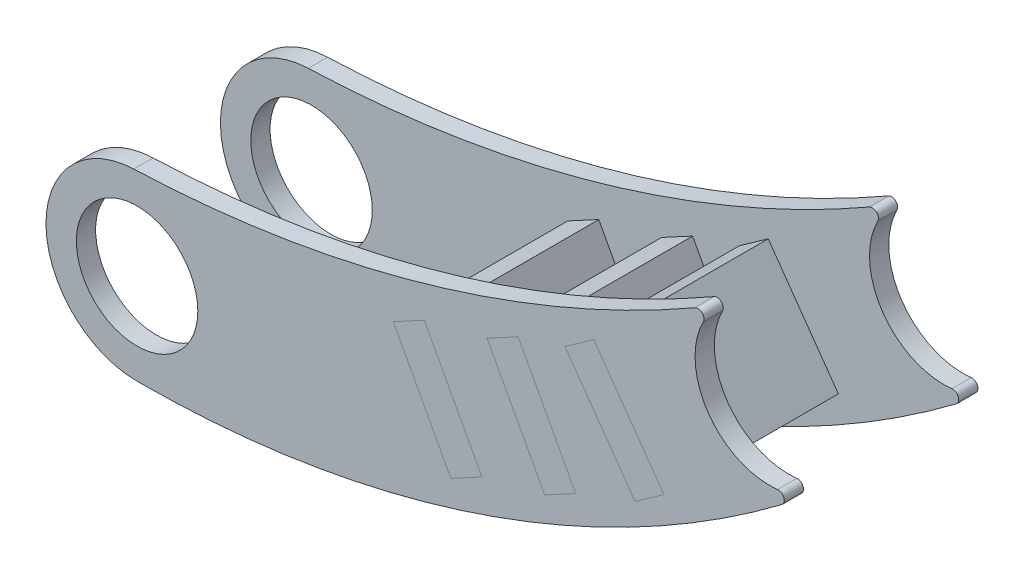
SolidWorks part; units mm, degrees
ref_plane "Front Plane" through (0, 0, 0) normal (0, 0, 1) x (1, 0, 0)
ref_plane "Top Plane" through (0, 0, 0) normal (0, 1, 0) x (1, 0, 0)
ref_plane "Right Plane" through (0, 0, 0) normal (1, 0, 0) x (0, 0, -1)
sketch "Sketch1" plane through (0, 0, 0) normal (0, 0, 1) x (1, 0, 0)
  line L17 (0, 0) -> (120, 0) construction
  line L18 (51.668, -3.0181) -> (42.1892, 14.5931)
  line L19 (51.668, -3.0181) -> (56.7793, -0.2671)
  line L20 (42.1892, 14.5931) -> (47.3005, 17.3441)
  line L21 (56.7793, -0.2671) -> (47.3005, 17.3441)
  line L22 (51.668, -3.0181) -> (47.3005, 17.3441) construction
  line L23 (42.1892, 14.5931) -> (56.7793, -0.2671) construction
  line L24 (67.1116, 2.3473) -> (57.6329, 19.9584)
  line L25 (67.1116, 2.3473) -> (72.2229, 5.0983)
  line L26 (57.6329, 19.9584) -> (62.7442, 22.7095)
  line L27 (72.2229, 5.0983) -> (62.7442, 22.7095)
  line L28 (67.1116, 2.3473) -> (62.7442, 22.7095) construction
  line L29 (57.6329, 19.9584) -> (72.2229, 5.0983) construction
  line L30 (82.0013, 8.8617) -> (70.4555, 25.1925)
  line L31 (82.0013, 8.8617) -> (86.741, 12.2126)
  line L32 (70.4555, 25.1925) -> (75.1953, 28.5434)
  line L33 (86.741, 12.2126) -> (75.1953, 28.5434)
  line L34 (82.0013, 8.8617) -> (75.1953, 28.5434) construction
  line L35 (70.4555, 25.1925) -> (86.741, 12.2126) construction
  circle A13 centre (0, 0) radius 10
  arc A22 (93.234, 40.0795) -> (105.4552, 22.2896) centre (104.1225, 34.4669) ccw
  arc A23 (-0.5383, 14.9903) -> (0, -15) centre (0, 0) ccw
  arc A24 (-0.5383, 14.9903) -> (91.8473, 41.405) centre (-7.7159, 214.8615) ccw
  arc A25 (0, -15) -> (106.1655, 20.4966) centre (0, 161.5115) ccw
  arc A26 (0, 0) -> (104.1225, 34.4669) centre (0, 174.5077) ccw construction
  arc A27 (15, 0) -> (14.9861, 0.6447) centre (0, 0) ccw
  arc A28 (106.1655, 20.4966) -> (105.4552, 22.2896) centre (105.564, 21.2955) ccw
  arc A29 (91.8473, 41.405) -> (93.234, 40.0795) centre (92.3451, 40.5377) cw
  point P11 (40.1143, 4.5615)
  point P12 (49.4843, 7.163)
  point P14 (64.9279, 12.5284)
  point P15 (78.5983, 18.7025)
  point P20 (56.2316, 11.0275)
  point P26 (0, 0)
  point P31 (39.7364, 4.5843)
  point P32 (55.7341, 8.8617)
  point P33 (61.1272, 11.0331)
  point P35 (0, 0)
  point P36 (57.265, 9.6634)
  point P37 (65.5493, 12.2126)
  dimension "D1" = 20
  dimension "D2" = 34.4669
  dimension "D5" = 30
  dimension "D7" = 120
  dimension "D12" = 15
  dimension "D9" = 5.8046
  dimension "D10" = 20
  dimension "D11" = 30
  dimension "D13" = 1
  dimension "D3" = 104.1225
  dimension "D4" = 24.5
  dimension "D6" = 200
  dimension "D8" = 50
extrude "Boss-Extrude1" add sketch "Sketch1" along normal blind 3.175 contours A29 A24 A23 A25 A28 A22 A13 L33 L31 L30 L32 L27 L25 L24 L26 L21 L19 L18 L20 region at (44.7261, 8.7283, 0)
ref_plane "Plane1" through (0, 0, -12.775) normal (0, 0, -1) x (-1, 0, 0)
mirror "Mirror3" about plane through (0, 0, -12.775) normal (0, 0, -1) of bodies 101
sketch "Sketch2" plane through (0, 0, 3.175) normal (0, 0, 1) x (1, 0, 0)
  line L4 (42.1892, 14.5931) -> (51.668, -3.0181)
  line L23 (42.1892, 14.5931) -> (47.3005, 17.3441)
  line L24 (51.668, -3.0181) -> (56.7793, -0.2671)
  line L25 (47.3005, 17.3441) -> (56.7793, -0.2671)
  line L26 (42.1892, 14.5931) -> (56.7793, -0.2671) construction
  line L27 (51.668, -3.0181) -> (47.3005, 17.3441) construction
  line L28 (57.6329, 19.9584) -> (67.1116, 2.3473)
  line L29 (57.6329, 19.9584) -> (62.7442, 22.7095)
  line L30 (67.1116, 2.3473) -> (72.2229, 5.0983)
  line L31 (62.7442, 22.7095) -> (72.2229, 5.0983)
  line L32 (57.6329, 19.9584) -> (72.2229, 5.0983) construction
  line L33 (67.1116, 2.3473) -> (62.7442, 22.7095) construction
  line L34 (70.4555, 25.1925) -> (82.0013, 8.8617)
  line L35 (70.4555, 25.1925) -> (75.1953, 28.5434)
  line L36 (82.0013, 8.8617) -> (86.741, 12.2126)
  line L37 (75.1953, 28.5434) -> (86.741, 12.2126)
  line L38 (70.4555, 25.1925) -> (86.741, 12.2126) construction
  line L39 (82.0013, 8.8617) -> (75.1953, 28.5434) construction
  line L40 (67.1116, 2.3473) -> (62.7442, 22.7095) construction
  line L41 (67.1116, 2.3473) -> (57.6329, 19.9584) construction
  line L42 (82.0013, 8.8617) -> (70.4555, 25.1925) construction
  line L43 (86.741, 12.2126) -> (75.1953, 28.5434) construction
  line L44 (51.668, -3.0181) -> (42.1892, 14.5931) construction
  line L45 (51.668, -3.0181) -> (56.7793, -0.2671) construction
  line L46 (70.4555, 25.1925) -> (75.1953, 28.5434) construction
  point P0 (79.691, 6.0151)
  point P1 (49.4843, 7.163)
  point P2 (64.9279, 12.5284)
  point P3 (78.5983, 18.7025)
ref_plane "Plane2" [suppressed] through (0, 0, -6.3875) normal (0, 0, -1) x (-1, 0, 0)
extrude "Boss-Extrude2" add sketch "Sketch2" against normal up to surface (31.9 mm away) separate body up to face at (63.6322, 17.8103, -28.725)
